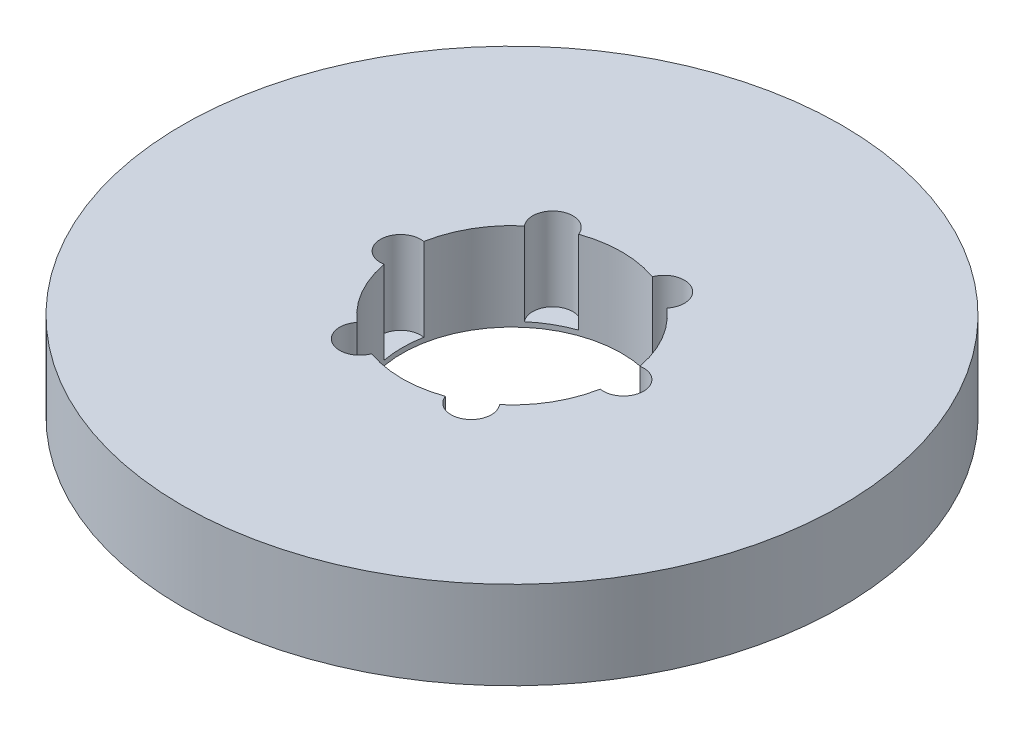
SolidWorks part; units mm, degrees
ref_plane "Front Plane" through (0, 0, 0) normal (0, 0, 1) x (1, 0, 0)
ref_plane "Top Plane" through (0, 0, 0) normal (0, 1, 0) x (1, 0, 0)
ref_plane "Right Plane" through (0, 0, 0) normal (1, 0, 0) x (0, 0, -1)
sketch "Sketch1" plane through (0, 0, 0) normal (0, 1, 0) x (1, 0, 0)
  circle A0 centre (0, 0) radius 75
  dimension "FLANGE_OD" = 150
extrude "Boss-Extrude1" add sketch "Sketch1" along normal blind 20
sketch "Sketch2" plane through (0, 0, 0) normal (0, 1, 0) x (1, 0, 0)
  circle A0 centre (0, 0) radius 25
  dimension "BORE_D" = 50
extrude "Cut-Extrude1" cut sketch "Sketch2" along normal through all
sketch "Sketch3" plane through (0, 20, 0) normal (0, 1, 0) x (1, 0, 0)
  circle A0 centre (0, 0) radius 25.3566 construction
  circle A1 centre (-25.3566, 0) radius 4.5827
  dimension "BOLT_D" = 9.1654
  dimension "BOLT_PCD" = 50.7131
extrude "Cut-Extrude2" cut sketch "Sketch3" against normal blind 18.89
pattern_circular "CirPattern1" count 6 over 360 about axis through (0, 0, 0) along (0, 1, 0) of "Cut-Extrude2"
